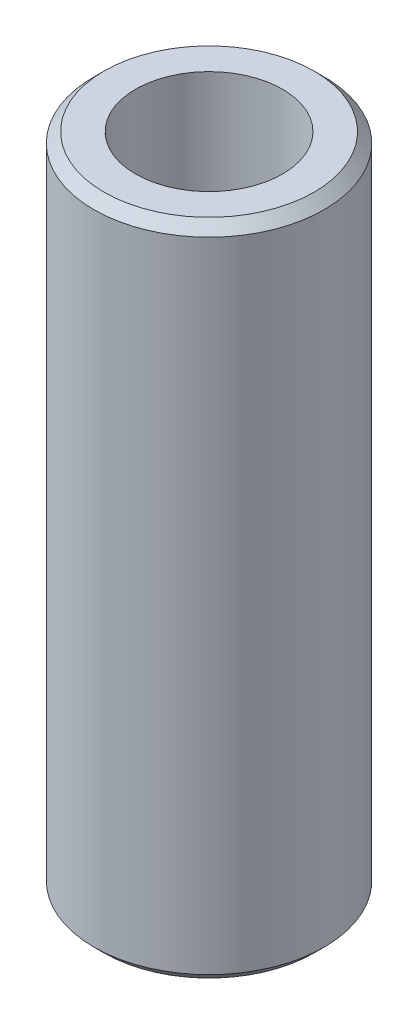
SolidWorks part; units mm, degrees
ref_plane "Front Plane" through (0, 0, 0) normal (0, 0, 1) x (1, 0, 0)
ref_plane "Top Plane" through (0, 0, 0) normal (0, 1, 0) x (1, 0, 0)
ref_plane "Right Plane" through (0, 0, 0) normal (1, 0, 0) x (0, 0, -1)
sketch "Sketch1" plane through (0, 0, 0) normal (0, 1, 0) x (1, 0, 0)
  circle A0 centre (0, 0) radius 50
  dimension "SHAFT_OD" = 100
extrude "Boss-Extrude1" add sketch "Sketch1" along normal blind 286.2174
sketch "Sketch2" plane through (0, 0, 0) normal (0, 1, 0) x (1, 0, 0)
  circle A0 centre (0, 0) radius 31.9322
  dimension "BORE_D" = 63.8644
extrude "Cut-Extrude1" cut sketch "Sketch2" along normal through all
chamfer "Chamfer1" distance 4.3886 angle 45 2 edges at (0, 286.2174, 50) (0, 0, 50)
